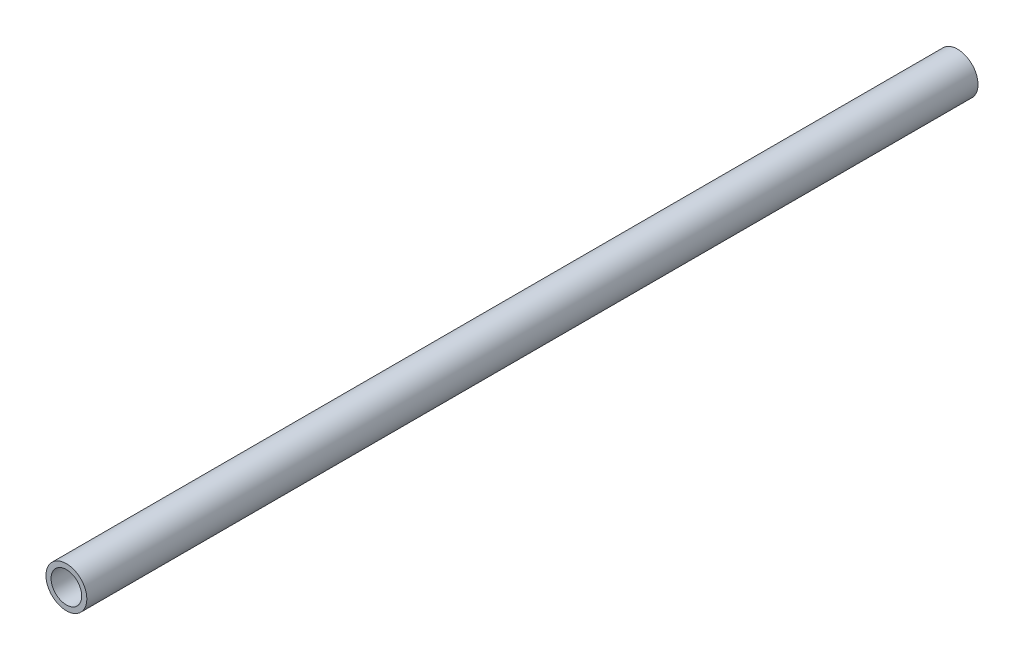
SolidWorks part; units mm, degrees
material "PC High Viscosity"
ref_plane "Front Plane" through (0, 0, 0) normal (0, 0, 1) x (1, 0, 0)
ref_plane "Top Plane" through (0, 0, 0) normal (0, 1, 0) x (1, 0, 0)
ref_plane "Right Plane" through (0, 0, 0) normal (1, 0, 0) x (0, 0, -1)
sketch "Sketch2" plane through (0, 0, 0) normal (0, 0, 1) x (1, 0, 0)
  circle A0 centre (0, 0) radius 9.525
  circle A1 centre (0, 0) radius 12.7
  dimension "D1" = 25.4
  dimension "D2" = 19.05
extrude "Boss-Extrude1" add sketch "Sketch2" along normal mid plane 554.0121
